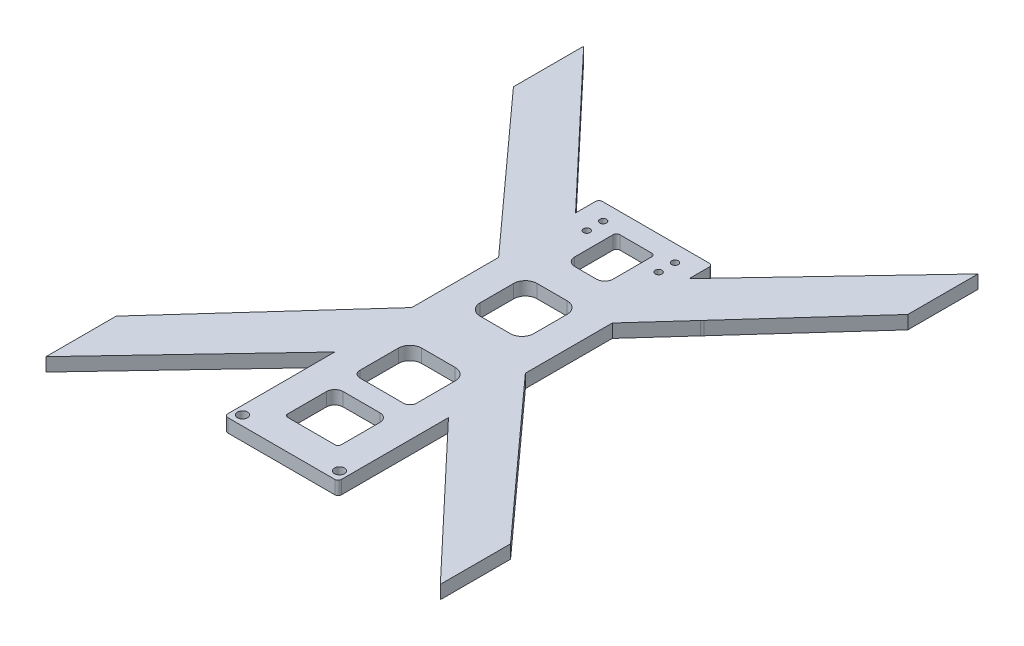
SolidWorks part; units mm, degrees
ref_plane "Front Plane" through (0, 0, 0) normal (0, 0, 1) x (1, 0, 0)
ref_plane "Top Plane" through (0, 0, 0) normal (0, 1, 0) x (1, 0, 0)
ref_plane "Right Plane" through (0, 0, 0) normal (1, 0, 0) x (0, 0, -1)
sketch "Frame Sketch" plane through (0, 0, 0) normal (0, 1, 0) x (1, 0, 0)
  line L0 (6.2981, 0.1404) -> (6.2981, 126.6085) construction
  line L6 (-48.6747, 0) -> (67.0859, 0) construction
  line L11 (6.2981, 0.1404) -> (6.2981, -105.8001) construction
  line L23 (-9.7019, 56.1404) -> (22.2981, 56.1404)
  line L24 (-10.7019, 55.1404) -> (-10.7019, -54.8596)
  line L25 (-9.7019, -55.8596) -> (22.2981, -55.8596)
  line L26 (23.2981, 55.1404) -> (23.2981, -54.8596)
  line L27 (-10.7019, 56.1404) -> (23.2981, -55.8596) construction
  line L28 (-10.7019, -55.8596) -> (23.2981, 56.1404) construction
  line L34 (23.2981, -22.8596) -> (65.2709, -67.262)
  line L37 (65.2709, -46.262) -> (65.2709, -67.262)
  line L38 (23.2981, 0.1404) -> (65.2709, -46.262)
  line L43 (23.2981, -22.8596) -> (23.2981, 0.1404)
  line L44 (-0.8423, -46.8596) -> (13.4385, -46.8596)
  line L45 (-1.7019, -46) -> (-1.7019, -34.3596)
  line L46 (0.7981, -31.8596) -> (11.7981, -31.8596)
  line L47 (14.2981, -46) -> (14.2981, -34.3596)
  line L48 (-1.7019, -46.8596) -> (14.2981, -31.8596) construction
  line L49 (-1.7019, -31.8596) -> (14.2981, -46.8596) construction
  line L50 (12.7981, -25.8596) -> (-0.2019, -25.8596)
  line L51 (14.7981, -23.8596) -> (14.7981, -12.3596)
  line L52 (11.2981, -8.8596) -> (1.2981, -8.8596)
  line L53 (-2.2019, -23.8596) -> (-2.2019, -12.3596)
  line L54 (14.7981, -25.8596) -> (-2.2019, -8.8596) construction
  line L55 (14.7981, -8.8596) -> (-2.2019, -25.8596) construction
  line L56 (1.7981, 8.1404) -> (10.7981, 8.1404)
  line L57 (-1.7019, 11.6404) -> (-1.7019, 21.6404)
  line L58 (1.7981, 25.1404) -> (10.7981, 25.1404)
  line L59 (14.2981, 11.6404) -> (14.2981, 21.6404)
  line L60 (-1.7019, 8.1404) -> (14.2981, 25.1404) construction
  line L61 (-1.7019, 25.1404) -> (14.2981, 8.1404) construction
  line L62 (3.0481, 35.1404) -> (9.5481, 35.1404)
  line L63 (0.5481, 37.6404) -> (0.5481, 49.1404)
  line L64 (1.5481, 50.1404) -> (11.0481, 50.1404)
  line L65 (12.0481, 37.6404) -> (12.0481, 49.1404)
  line L66 (0.5481, 35.1404) -> (12.0481, 50.1404) construction
  line L67 (0.5481, 50.1404) -> (12.0481, 35.1404) construction
  line L69 (23.2981, 49.1404) -> (65.2709, 93.5427)
  line L70 (23.2981, 26.1404) -> (65.2709, 72.5427)
  line L71 (65.2709, 72.5427) -> (65.2709, 93.5427)
  line L72 (23.2981, 26.1404) -> (23.2981, 49.1404)
  line L73 (-10.7019, 26.1404) -> (-52.6747, 72.5427)
  line L74 (-52.6747, 72.5427) -> (-52.6747, 93.5427)
  line L75 (-10.7019, 49.1404) -> (-52.6747, 93.5427)
  line L76 (-10.7019, 26.1404) -> (-10.7019, 49.1404)
  line L77 (-10.7019, -22.8596) -> (-52.6747, -67.262)
  line L78 (-52.6747, -46.262) -> (-52.6747, -67.262)
  line L79 (-10.7019, 0.1404) -> (-52.6747, -46.262)
  line L80 (-10.7019, -22.8596) -> (-10.7019, 0.1404)
  line L81 (-23.7019, 40.5123) -> (-10.7019, 26.1404)
  line L82 (-10.7019, 0.1404) -> (-23.7019, -14.2315)
  line L83 (-23.7019, 40.5123) -> (-10.7019, 26.1404)
  line L84 (-10.7019, 0.1404) -> (-23.7019, -14.2315)
  line L85 (-23.7019, 40.5123) -> (-10.7019, 26.1404)
  line L86 (-10.7019, 0.1404) -> (-23.7019, -14.2315)
  line L87 (-23.7019, 40.5123) -> (-10.7019, 26.1404)
  arc A8 (23.2981, 55.1404) -> (22.2981, 56.1404) centre (22.2981, 55.1404) ccw
  arc A9 (23.2981, -54.8596) -> (22.2981, -55.8596) centre (22.2981, -54.8596) cw
  arc A10 (-9.7019, 56.1404) -> (-10.7019, 55.1404) centre (-9.7019, 55.1404) ccw
  arc A11 (-9.7019, -55.8596) -> (-10.7019, -54.8596) centre (-9.7019, -54.8596) cw
  circle A12 centre (-8.2019, -52.9596) radius 1.5
  circle A13 centre (20.7981, -52.9596) radius 1.5
  arc A14 (14.2981, -46) -> (13.4385, -46.8596) centre (13.4385, -46) cw
  arc A15 (-0.8423, -46.8596) -> (-1.7019, -46) centre (-0.8423, -46) cw
  arc A16 (-1.7019, -34.3596) -> (0.7981, -31.8596) centre (0.7981, -34.3596) cw
  arc A17 (11.7981, -31.8596) -> (14.2981, -34.3596) centre (11.7981, -34.3596) cw
  arc A18 (14.7981, -23.8596) -> (12.7981, -25.8596) centre (12.7981, -23.8596) cw
  arc A19 (-2.2019, -23.8596) -> (-0.2019, -25.8596) centre (-0.2019, -23.8596) ccw
  arc A20 (14.7981, -12.3596) -> (11.2981, -8.8596) centre (11.2981, -12.3596) ccw
  arc A21 (1.2981, -8.8596) -> (-2.2019, -12.3596) centre (1.2981, -12.3596) ccw
  arc A22 (1.7981, 8.1404) -> (-1.7019, 11.6404) centre (1.7981, 11.6404) cw
  arc A23 (14.2981, 11.6404) -> (10.7981, 8.1404) centre (10.7981, 11.6404) cw
  arc A24 (1.7981, 25.1404) -> (-1.7019, 21.6404) centre (1.7981, 21.6404) ccw
  arc A25 (14.2981, 21.6404) -> (10.7981, 25.1404) centre (10.7981, 21.6404) ccw
  arc A26 (3.0481, 35.1404) -> (0.5481, 37.6404) centre (3.0481, 37.6404) cw
  arc A27 (12.0481, 37.6404) -> (9.5481, 35.1404) centre (9.5481, 37.6404) cw
  arc A28 (1.5481, 50.1404) -> (0.5481, 49.1404) centre (1.5481, 49.1404) ccw
  arc A29 (12.0481, 49.1404) -> (11.0481, 50.1404) centre (11.0481, 49.1404) ccw
  circle A30 centre (17.0481, 51.1404) radius 1
  circle A31 centre (17.0481, 46.2404) radius 1
  circle A32 centre (-4.4519, 51.1404) radius 1
  circle A33 centre (-4.4519, 46.2404) radius 1
  spline S0 degree 3 poles (-23.7019, 40.5123) (-9.7905, 25.4071) (-9.7035, 0.8596) (-23.7019, -14.2315) knots 0 0 0 0 1 1 1 1
  spline S1 degree 3 poles (36.2981, 40.5123) (22.3867, 25.4071) (22.2997, 0.8596) (36.2981, -14.2315) knots 0 0 0 0 1 1 1 1
  point P0 (0, 0)
  point P6 (0, 0)
  point P52 (6.2981, -39.3596)
  point P69 (6.2981, -17.3596)
  point P86 (6.2981, 16.6404)
  point P103 (6.2981, 42.6404)
  dimension "D6" = 1
  dimension "D7" = 2.9
  dimension "D8" = 2.5
  dimension "D5" = 17
  dimension "D11" = 9
  dimension "D12" = 9
  dimension "D13" = 10
  dimension "D14" = 33
  dimension "D17" = 23
  dimension "D18" = 21
  dimension "D19" = 26
  dimension "D20" = 7
  dimension "D23" = 23
  dimension "D24" = 21
  dimension "D25" = 1
  dimension "D30" = 5
  dimension "D31" = 5
  dimension "D32" = 4.9
  dimension "D33" = 6
  dimension "D34" = 5
  dimension "D3" = 112
  dimension "D4" = 34
  dimension "D9" = 15
  dimension "D10" = 16
  dimension "D15" = 17
  dimension "D16" = 6
  dimension "D21" = 17
  dimension "D22" = 16
  dimension "D27" = 17
  dimension "D28" = 15
  dimension "D29" = 11.5
  dimension "D35" = 13
extrude "Frame Bottom Plate" add sketch "Frame Sketch" along normal blind 4 contours L26 L23 L24 L25 | L37 | L70 L71 L69 L26 | L24 L79 L78 L77 | L34 L37 L38 L43 | L73 L74 L75 L76 region at (6.2981, 0, -1.1832) region at (43.9665, 0, -59.9976) region at (-31.3704, 0, 33.7169)
